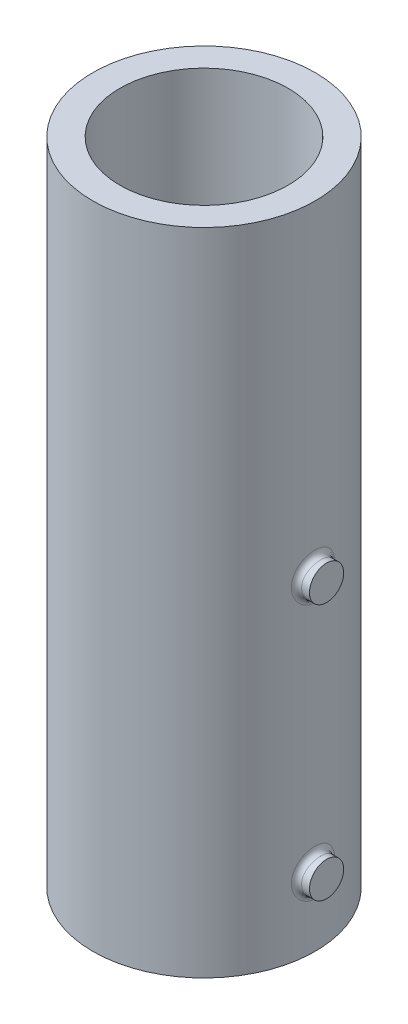
SolidWorks part; units mm, degrees
ref_plane "Front Plane" through (0, 0, 0) normal (0, 0, 1) x (1, 0, 0)
ref_plane "Top Plane" through (0, 0, 0) normal (0, 1, 0) x (1, 0, 0)
ref_plane "Right Plane" through (0, 0, 0) normal (1, 0, 0) x (0, 0, -1)
sketch "Sketch1" plane through (0, 0, 0) normal (0, 1, 0) x (1, 0, 0)
  circle A0 centre (0, 0) radius 14.5 construction
  circle A1 centre (0, 0) radius 19.5
  circle A2 centre (0, 0) radius 14.75
  dimension "D1" = 5
  dimension "D2" = 29
  dimension "D3" = 0.25
extrude "Boss-Extrude1" add sketch "Sketch1" along normal mid plane 114
ref_plane "Plane1" through (19.5, 0, 0) normal (1, 0, 0) x (0, 0, -1)
sketch "Sketch2" plane through (19.5, 0, 0) normal (1, 0, 0) x (0, 0, -1)
  line L0 (0, 0) -> (0, -50000) construction
  line L1 (0, 0) -> (28.2007, 0) construction
  circle A0 centre (0, -45) radius 3
  circle A1 centre (0, 0) radius 3
  dimension "D1" = 6
  dimension "D3" = 6
  dimension "D2" = 45
extrude "Boss-Extrude2" add sketch "Sketch2" along normal blind 2 and the other way up to surface separate body other way up to face at (0, 57, 19.5)
ref_plane "Plane2" through (-19.5, 0, 0) normal (-1, 0, 0) x (0, 0, 1)
sketch "Sketch3" plane through (-19.5, 0, 0) normal (-1, 0, 0) x (0, 0, 1)
  circle A0 centre (0, 0) radius 3
  dimension "D1" = 6
extrude "Boss-Extrude4" add sketch "Sketch3" along normal blind 2 and the other way up to surface separate body other way up to face at (0, 57, 19.5)
combine bodies "Combine1" operation type add bodies to combine 108 101 109 107
fillet "Fillet3" radius 1 3 edges at (-19.2788, 0.6504, 2.9286) (19.2788, -45.6504, -2.9286) (19.2788, 0.6504, -2.9286)
equation "\"D3@Sketch2\"=\"globalStud\""
equation "\"globalStud\"= 6"
equation "\"D1@Sketch3\"=\"globalStud\""
equation "\"globalExtrude\" = 2"
equation "\"D1@Sketch2\"=\"globalStud\""
equation "\"D1@Boss-Extrude4\"=\"globalExtrude\""
equation "\"D1@Boss-Extrude2\"=\"globalExtrude\""
equation "\"connectionLink\"=7.6"
